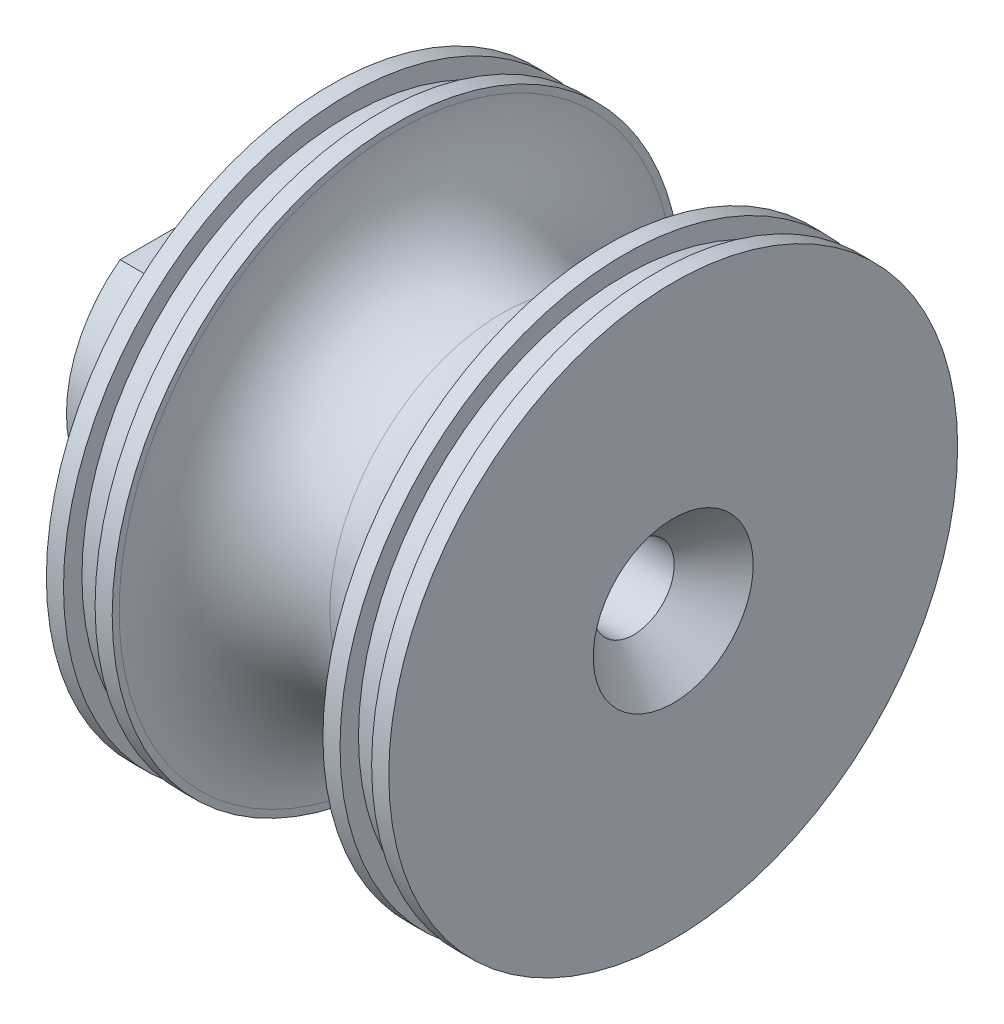
SolidWorks part; units mm, degrees
material "ABS"
ref_plane "Front Plane" through (0, 0, 0) normal (0, 0, 1) x (1, 0, 0)
ref_plane "Top Plane" through (0, 0, 0) normal (0, 1, 0) x (1, 0, 0)
ref_plane "Right Plane" through (0, 0, 0) normal (1, 0, 0) x (0, 0, -1)
sketch "Sketch1" plane through (0, 0, 0) normal (0, 0, 1) x (1, 0, 0)
  line L1 (0, 21.6) -> (1.3, 21.6)
  line L2 (1.3, 21.6) -> (1.3, 20.2)
  line L3 (1.3, 20.2) -> (3.7, 20.2)
  line L4 (3.7, 20.2) -> (3.7, 21.6)
  line L5 (3.7, 21.6) -> (5, 21.6)
  line L6 (5, 21.6) -> (5, 13.075)
  line L7 (5, 13.075) -> (21, 13.075)
  line L8 (21, 13.075) -> (21, 21.6)
  line L9 (21, 21.6) -> (22.3, 21.6)
  line L10 (22.3, 21.6) -> (22.3, 20.2)
  line L11 (22.3, 20.2) -> (24.7, 20.2)
  line L12 (24.7, 20.2) -> (24.7, 21.6)
  line L13 (24.7, 21.6) -> (26, 21.6)
  line L14 (26, 21.6) -> (26, 3.075)
  line L15 (26, 3.075) -> (-10, 3.075)
  line L16 (-10, 3.075) -> (-10, 10.075)
  line L17 (-10, 10.075) -> (0, 10.075)
  line L18 (0, 10.075) -> (0, 21.6)
  line L19 (0, 0) -> (26.8995, 0)
  point P7 (0, 15.8375)
  dimension "D1" = 3.075
  dimension "D2" = 10
  dimension "D3" = 26
  dimension "D4" = 1.3
  dimension "D5" = 2.4
  dimension "D6" = 1.3
  dimension "D7" = 21.6
  dimension "D8" = 1.4
  dimension "D9" = 1.3
  dimension "D10" = 2.4
  dimension "D11" = 1.3
  dimension "D12" = 10
  dimension "D13" = 0
  dimension "D14" = 7
revolve "Revolve1" add sketch "Sketch1" angle 360 about L19
fillet "Fillet3" radius 8 1 edges at (5, 0, 13.075)
fillet "Fillet4" radius 8 1 edges at (21, 0, 13.075)
sketch "Sketch3" plane through (-10, 0, 0) normal (-1, 0, 0) x (0, 0, 1)
  line L0 (-6, 8.0936) -> (6, 8.0936)
  line L1 (-6, 8.0936) -> (-6, 11.736)
  line L2 (-6, 11.736) -> (6, 11.736)
  line L3 (6, 11.736) -> (6, 8.0936)
  circle A0 centre (0, 0) radius 10.075 construction
  dimension "D1" = 12
extrude "Cut-Extrude1" cut sketch "Sketch3" against normal blind 10
sketch "Sketch4" plane through (0, 8.0936, 0) normal (0, 1, 0) x (1, 0, 0)
  line L0 (0, -6) -> (-10, -6) construction
  line L3 (-10, 6) -> (-10, -6) construction
  circle A0 centre (-5, 0) radius 1.5
  point P2 (-5, -6)
  dimension "D1" = 3
  dimension "D2" = 6
  dimension "D3" = 5
extrude "Cut-Extrude2" cut sketch "Sketch4" against normal up to next
chamfer "Chamfer1" distance 3 angle 45 1 edges at (26, 0, 3.075)
